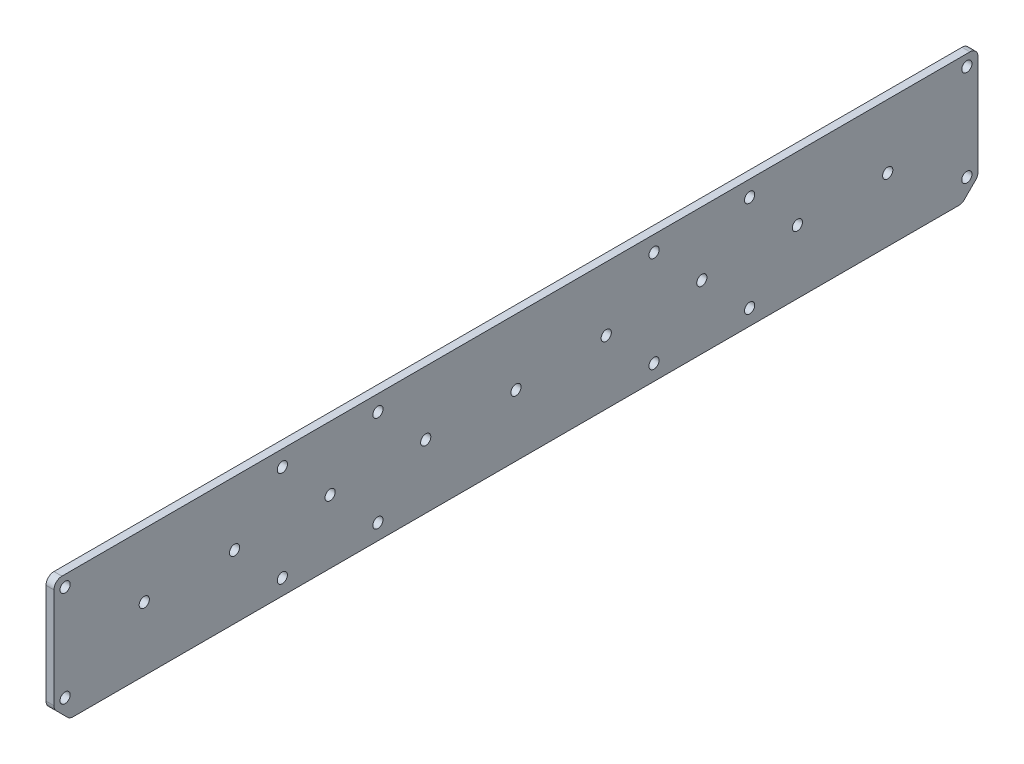
SolidWorks part; units mm, degrees
ref_plane "Front Plane" through (0, 0, 0) normal (0, 0, 1) x (1, 0, 0)
ref_plane "Top Plane" through (0, 0, 0) normal (0, 1, 0) x (1, 0, 0)
ref_plane "Right Plane" through (0, 0, 0) normal (1, 0, 0) x (0, 0, -1)
sketch "Sketch1" plane through (0, 0, 0) normal (1, 0, 0) x (0, 0, -1)
  line L1 (0, 0) -> (368.3, 0)
  line L2 (0, 0) -> (0, 50.8)
  line L3 (0, 50.8) -> (368.3, 50.8)
  line L4 (368.3, 0) -> (368.3, 50.8)
  dimension "D1" = 50.8
  dimension "D2" = 368.3
extrude "Boss-Extrude1" add sketch "Sketch1" along normal blind 3.175
chamfer "Chamfer1" distance 6.35 angle 45 2 edges at (1.5875, 0, -368.3) (1.5875, 0, 0)
fillet "Fillet1" radius 3.175 6 edges at (1.5875, 0, -361.95) (1.5875, 6.35, -368.3) (1.5875, 50.8, -368.3) (1.5875, 0, -6.35) (1.5875, 6.35, 0) (1.5875, 50.8, 0)
sketch "Sketch2" plane through (3.175, 0, 0) normal (1, 0, 0) x (0, 0, -1)
  point P6 (91.0254, 6.284)
  point P9 (91.0254, 44.516)
  point P12 (71.9754, 25.4)
  point P15 (35.9921, 25.4)
  point P18 (148.1754, 25.4)
  point P21 (129.1254, 6.284)
  point P24 (110.0754, 25.4)
  point P27 (129.1254, 44.516)
  point P33 (184.15, 24.6062)
  point P42 (220.1246, 25.4)
  point P48 (239.1746, 6.284)
  point P51 (239.1746, 44.516)
  point P54 (258.2246, 25.4)
  point P57 (277.2746, 6.284)
  point P60 (277.2746, 44.516)
  point P63 (296.3246, 25.4)
  point P69 (332.3079, 25.4)
  point P75 (363.855, 46.355)
  point P78 (4.445, 46.355)
  point P81 (4.445, 8.1912)
  point P84 (363.855, 8.1912)
hole_wizard "#8 (0.16) Diameter Hole1" positions "Sketch2" profile "Sketch3" hole size "#8" standard "ANSI Inch" end condition through all
sketch "Sketch3" plane through (3.175, 6.284, -91.0254) normal (0, 1, 0) x (0, 0, -1)
  line L0 (0, 0) -> (0, 3.175)
  line L1 (0, 3.175) -> (2.032, 3.175)
  line L2 (2.032, 3.175) -> (2.032, 0)
  line L5 (2.032, 0) -> (0, 0)
  line L11 (0, -6.35) -> (0, 107.95) construction
  dimension "Thru Hole Dia." = 4.064
  dimension "Thru Hole Depth" = 3.175
